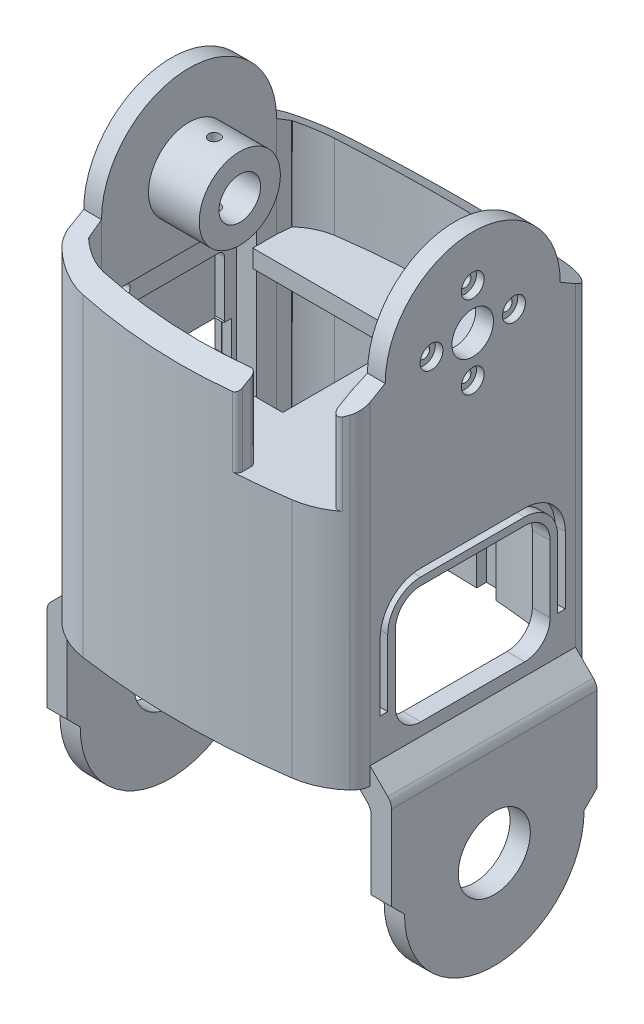
SolidWorks part; units mm, degrees
material "PLA"
ref_plane "Front Plane" through (0, 0, 0) normal (0, 0, 1) x (1, 0, 0)
ref_plane "Top Plane" through (0, 0, 0) normal (0, 1, 0) x (1, 0, 0)
ref_plane "Right Plane" through (0, 0, 0) normal (1, 0, 0) x (0, 0, -1)
sketch "Sketch1" plane through (0, 0, 0) normal (1, 0, 0) x (0, 0, -1)
  line L0 (-17.25, 0) -> (-17.25, -67.25)
  line L1 (17.25, 0) -> (17.25, -67.25)
  line L2 (-17.25, -67.25) -> (17.25, -67.25)
  arc A0 (17.25, 0) -> (-17.25, 0) centre (0, 0) ccw
  circle A1 centre (0, 0) radius 4.1
  circle A2 centre (0, 0) radius 8.125 construction
  circle A3 centre (0, 8.125) radius 1.15
  circle A4 centre (8.125, 0) radius 1.15
  circle A5 centre (-8.125, 0) radius 1.15
  circle A6 centre (0, -8.125) radius 1.15
  dimension "D1" = 34.5
  dimension "D4" = 8.2
  dimension "D5" = 16.25
  dimension "D6" = 2.3
  dimension "D2" = 67.25
  dimension "D3" = 67.25
extrude "Boss-Extrude1" add sketch "Sketch1" along normal blind 3.5
ref_plane "Plane1" through (0, 0, 0) normal (0, -1, 0) x (-1, 0, 0)
ref_plane "Plane2" through (29.7, 0, 0) normal (-1, 0, 0) x (0, 0, 1)
sketch "Sketch2" plane through (0, 0, 0) normal (0, -1, 0) x (-1, 0, 0)
  line L0 (0, -17.25) -> (-59.4, -17.25) construction
  line L1 (-29.7, 0) -> (-29.7, -28) construction
  line L3 (-59.4, -17.25) -> (-59.4, -20.25)
  line L4 (0, -17.25) -> (0, -20.25)
  line L6 (-29.7, -28) -> (-17.6897, -27.7644) construction
  line L7 (-17.6897, -27.7644) -> (-9.1109, -26.529) construction
  line L8 (-9.1109, -26.529) -> (-3.2086, -24.1613) construction
  line L9 (-3.2086, -24.1613) -> (-1.3201, -22.8861) construction
  line L10 (-1.3201, -22.8861) -> (-0.3051, -21.5079) construction
  line L11 (-0.3051, -21.5079) -> (-0.1375, -21.1541) construction
  line L12 (-0.1375, -21.1541) -> (0, -20.25) construction
  line L13 (-3.5, -17.25) -> (-3.7359, -19.9547)
  line L14 (-55.9, -17.25) -> (-55.6641, -19.9547)
  line L15 (-55.9, -17.25) -> (-59.4, -17.25)
  line L17 (0, -17.25) -> (-3.5, -17.25)
  arc A0 (0, -20.25) -> (-1.3201, -22.8861) centre (-4.0147, -19.8881) cw
  arc A1 (-1.3201, -22.8861) -> (-9.1109, -26.529) centre (-11.2153, -11.8765) cw
  arc A2 (-29.7, -28) -> (-9.1109, -26.529) centre (-29.7, 116.8281) ccw
  arc A3 (-29.7, -24.2523) -> (-9.3648, -22.779) centre (-29.7, 116.8281) ccw
  arc A4 (-3.8286, -20.1061) -> (-9.3648, -22.779) centre (-11.2153, -11.8765) cw
  arc A5 (-3.7359, -19.9547) -> (-3.8286, -20.1061) centre (-4.0147, -19.8881) cw
  arc A6 (-29.7, -28) -> (-50.2891, -26.529) centre (-29.7, 116.8281) cw
  arc A7 (-58.0799, -22.8861) -> (-50.2891, -26.529) centre (-48.1847, -11.8765) ccw
  arc A8 (-59.4, -20.25) -> (-58.0799, -22.8861) centre (-55.3853, -19.8881) ccw
  arc A9 (-55.6641, -19.9547) -> (-55.5714, -20.1061) centre (-55.3853, -19.8881) ccw
  arc A10 (-55.5714, -20.1061) -> (-50.0352, -22.779) centre (-48.1847, -11.8765) ccw
  arc A11 (-29.7, -24.2523) -> (-50.0352, -22.779) centre (-29.7, 116.8281) cw
  dimension "D1" = 59.4
extrude "Boss-Extrude2" add sketch "Sketch2" along normal blind 67.25
mirror "Mirror2" about plane through (29.7, 0, 0) normal (-1, 0, 0) of "Boss-Extrude1"
sketch "Sketch3" plane through (0, 0, 0) normal (-1, 0, 0) x (0, 0, 1)
  line L0 (17.25, 0) -> (32.7486, -8.9481)
  line L1 (-1.925, 0) -> (1.925, 0) construction
  line L2 (32.7486, -8.9481) -> (32.7486, 0)
  line L3 (32.7486, 0) -> (17.25, 0)
  arc A0 (17.25, 0) -> (-17.25, 0) centre (0, 0) ccw construction
  dimension "D1" = 30
extrude "Cut-Extrude1" cut sketch "Sketch3" against normal through all
ref_plane "Plane3" through (0, 0, 0) normal (0, 0, -1) x (-1, 0, 0)
mirror "Mirror3" about plane through (0, 0, 0) normal (0, 0, -1) of "Cut-Extrude1", "Boss-Extrude2"
sketch "Sketch4" plane through (0, 0, 0) normal (-1, 0, 0) x (0, 0, 1)
  line L0 (-20.25, -67.25) -> (-20.25, -1.7321) construction
  line L1 (-13.25, -13.5) -> (13.25, -13.5)
  line L2 (-13.25, -13.5) -> (-13.25, -60.75)
  line L3 (-13.25, -60.75) -> (13.25, -60.75)
  line L4 (13.25, -13.5) -> (13.25, -60.75)
  line L5 (20.25, -67.25) -> (20.25, -1.7321) construction
  line L6 (20.25, -67.25) -> (-20.25, -67.25) construction
  dimension "D1" = 7
  dimension "D2" = 7
  dimension "D3" = 13.5
  dimension "D4" = 6.5
extrude "Cut-Extrude2" cut sketch "Sketch4" against normal blind 3.5
sketch "Sketch6" plane through (0, 0, 0) normal (-1, 0, 0) x (0, 0, 1)
  line L8 (-15.75, -63.25) -> (15.75, -63.25)
  line L9 (-15.75, -11) -> (-15.75, -63.25)
  line L10 (15.75, -63.25) -> (15.75, -11)
  line L11 (15.75, -11) -> (-15.75, -11)
  line L12 (-15.75, -63.25) -> (15.75, -63.25)
  line L13 (-15.75, -11) -> (-15.75, -63.25)
  line L14 (15.75, -63.25) -> (15.75, -11)
  line L15 (15.75, -11) -> (-15.75, -11)
  dimension "D1" = 2.5
extrude "Boss-Extrude3" add sketch "Sketch6" along normal blind 2
chamfer "Chamfer2" distance 2 angle 45 4 edges at (-2, -63.25, 0) (-2, -37.125, 15.75) (-2, -37.125, -15.75) (-2, -11, 0)
sketch "Sketch7" plane through (0, 0, 0) normal (1, 0, 0) x (0, 0, -1)
  line L4 (-13.25, -60.75) -> (13.25, -60.75)
  line L5 (13.25, -60.75) -> (13.25, -13.5)
  line L6 (13.25, -13.5) -> (-13.25, -13.5)
  line L7 (-13.25, -13.5) -> (-13.25, -60.75)
  line L8 (-13.25, -60.75) -> (13.25, -60.75)
  line L9 (13.25, -60.75) -> (13.25, -13.5)
  line L10 (13.25, -13.5) -> (-13.25, -13.5)
  line L11 (-13.25, -13.5) -> (-13.25, -60.75)
  dimension "D1" = 0
extrude "Cut-Extrude3" cut sketch "Sketch7" against normal blind 0.8
sketch "Sketch8" plane through (-2, 0, 0) normal (-1, 0, 0) x (0, 0, 1)
  line L0 (15.75, -63.25) -> (15.75, -11) construction
  line L1 (-10.6511, -32.25) -> (10.75, -32.25)
  line L2 (-10.6511, -32.25) -> (-10.6511, -38.75)
  line L3 (-10.6511, -38.75) -> (10.75, -38.75)
  line L4 (10.75, -32.25) -> (10.75, -38.75)
  line L5 (-15.75, -11) -> (-15.75, -63.25) construction
  line L6 (15.75, -11) -> (-15.75, -11) construction
  line L7 (-15.75, -63.25) -> (15.75, -63.25) construction
  dimension "D1" = 5
  dimension "D2" = 5.0989
  dimension "D3" = 21.25
  dimension "D4" = 24.5
extrude "Cut-Extrude4" cut sketch "Sketch8" against normal up to next
sketch "Sketch9" plane through (59.4, 0, 0) normal (1, 0, 0) x (0, 0, -1)
  circle A0 centre (0, -49.64) radius 7.1
  dimension "D1" = 14.2
extrude "Cut-Extrude5" cut sketch "Sketch9" against normal up to next
ref_plane "Plane4" through (0, -19.75, 0) normal (0, -1, 0) x (-1, 0, 0)
sketch "Sketch10" plane through (0, -19.75, 0) normal (0, -1, 0) x (-1, 0, 0)
  line L0 (-55.6641, -19.9547) -> (-55.9, -17.25) construction
  line L1 (-3.5, -17.25) -> (-3.7359, -19.9547) construction
  line L3 (-3.5, -17.25) -> (-3.5, 17.25) construction
  line L6 (-3.5, 17.25) -> (-3.7359, 19.9547) construction
  line L7 (-55.9, -17.25) -> (-55.9, 17.25) construction
  line L8 (-55.6641, 19.9547) -> (-55.9, 17.25) construction
  line L9 (-55.6641, -19.9547) -> (-55.9, -17.25)
  line L10 (-3.5, -17.25) -> (-3.7359, -19.9547)
  line L11 (-3.5, -17.25) -> (-3.5, -12.56)
  line L12 (-3.5, 17.25) -> (-3.7359, 19.9547)
  line L13 (-55.9, -17.25) -> (-55.9, 17.25)
  line L14 (-55.6641, 19.9547) -> (-55.9, 17.25)
  line L15 (-18.2613, -12.36) -> (-18.2613, -12.56) construction
  line L16 (-12.72, -12.36) -> (-25.62, -12.36) construction
  line L17 (-3.5, -12.56) -> (-34.52, -12.56)
  line L18 (-34.52, -12.56) -> (-34.52, 12.56)
  line L19 (-3.5, 12.56) -> (-3.5, 17.25)
  line L43 (-34.52, 12.56) -> (-3.5, 12.56)
  line L45 (-25.62, 12.36) -> (-12.72, 12.36) construction
  line L46 (-34.52, 5) -> (-34.52, 13.1992) construction
  line L47 (-31.62, 5) -> (-35.82, 5) construction
  line L48 (-34.32, 6.7) -> (-34.32, 5.6557) construction
  arc A0 (-55.6641, -19.9547) -> (-55.5714, -20.1061) centre (-55.3853, -19.8881) ccw construction
  arc A1 (-50.0352, -22.779) -> (-9.3648, -22.779) centre (-29.7, 116.8281) ccw construction
  arc A2 (-55.5714, -20.1061) -> (-50.0352, -22.779) centre (-48.1847, -11.8765) ccw construction
  arc A3 (-9.3648, -22.779) -> (-3.8286, -20.1061) centre (-11.2153, -11.8765) ccw construction
  arc A4 (-3.8286, -20.1061) -> (-3.7359, -19.9547) centre (-4.0147, -19.8881) ccw construction
  arc A5 (-3.7359, 19.9547) -> (-3.8286, 20.1061) centre (-4.0147, 19.8881) ccw construction
  arc A6 (-3.8286, 20.1061) -> (-9.3648, 22.779) centre (-11.2153, 11.8765) ccw construction
  arc A7 (-9.3648, 22.779) -> (-50.0352, 22.779) centre (-29.7, -116.8281) ccw construction
  arc A8 (-55.5714, 20.1061) -> (-55.6641, 19.9547) centre (-55.3853, 19.8881) ccw construction
  arc A9 (-50.0352, 22.779) -> (-55.5714, 20.1061) centre (-48.1847, 11.8765) ccw construction
  arc A30 (-55.6641, -19.9547) -> (-55.5714, -20.1061) centre (-55.3853, -19.8881) ccw
  arc A31 (-50.0352, -22.779) -> (-9.3648, -22.779) centre (-29.7, 116.8281) ccw
  arc A32 (-55.5714, -20.1061) -> (-50.0352, -22.779) centre (-48.1847, -11.8765) ccw
  arc A33 (-9.3648, -22.779) -> (-3.8286, -20.1061) centre (-11.2153, -11.8765) ccw
  arc A34 (-3.8286, -20.1061) -> (-3.7359, -19.9547) centre (-4.0147, -19.8881) ccw
  arc A35 (-3.7359, 19.9547) -> (-3.8286, 20.1061) centre (-4.0147, 19.8881) ccw
  arc A36 (-3.8286, 20.1061) -> (-9.3648, 22.779) centre (-11.2153, 11.8765) ccw
  arc A37 (-9.3648, 22.779) -> (-50.0352, 22.779) centre (-29.7, -116.8281) ccw
  arc A38 (-55.5714, 20.1061) -> (-55.6641, 19.9547) centre (-55.3853, 19.8881) ccw
  arc A39 (-50.0352, 22.779) -> (-55.5714, 20.1061) centre (-48.1847, 11.8765) ccw
  dimension "D1" = 0.2
  dimension "D2" = 0.2
  dimension "D3" = 0.2
extrude "Boss-Extrude4" add sketch "Sketch10" along normal blind 3.5
sketch "Sketch11" plane through (0, -23.25, 0) normal (0, -1, 0) x (-1, 0, 0)
  line L0 (-36.07, -6.9) -> (-40.07, -6.9) construction
  line L2 (-36.07, -6.9) -> (-36.07, -24.1084) construction
  line L3 (-40.07, -6.9) -> (-40.07, -24.1084) construction
  line L5 (-36.07, -24.1084) -> (-40.07, -24.1084)
  line L6 (-36.07, -24.1084) -> (-36.07, 25.609)
  line L7 (-36.07, 25.609) -> (-40.07, 25.609)
  line L8 (-40.07, -24.1084) -> (-40.07, 25.609)
  arc A0 (-50.0352, -22.779) -> (-9.3648, -22.779) centre (-29.7, 116.8281) ccw construction
  dimension "D1" = 4
extrude "Boss-Extrude5" add sketch "Sketch11" along normal blind 40
sketch "Sketch12" plane through (40.07, 0, 0) normal (1, 0, 0) x (0, 0, -1)
  circle A0 centre (0, -49.64) radius 7.1
extrude "Cut-Extrude6" cut sketch "Sketch12" against normal blind 10
chamfer "Chamfer3" distance 1 angle 45 1 edges at (36.07, -23.25, 0)
chamfer "Chamfer4" distance 1 angle 45 1 edges at (40.07, -23.25, 0)
fillet "Fillet1" radius 3 2 edges at (38.0708, -63.25, -24.0037) (38.0708, -63.25, 24.0037)
sketch "Sketch13" plane through (59.4, 0, 0) normal (1, 0, 0) x (0, 0, -1)
  circle A0 centre (0, -49.64) radius 9
  circle A1 centre (0, -49.64) radius 5.5
  dimension "D1" = 18
  dimension "D2" = 11
extrude "Boss-Extrude6" add sketch "Sketch13" along normal blind 1.5
sketch "Sketch16" plane through (60.9, 0, 0) normal (1, 0, 0) x (0, 0, -1)
  circle A0 centre (0, -49.64) radius 9
extrude "Boss-Extrude7" add sketch "Sketch16" along normal blind 1
fillet "Fillet2" radius 1 1 edges at (61.9, -49.64, -9)
ref_plane "Plane5" through (0, 0, 20.25) normal (0, 0, -1) x (-1, 0, 0)
sketch "Sketch17" plane through (0, 0, 20.25) normal (0, 0, -1) x (-1, 0, 0)
  line L0 (-59.4, -67.25) -> (-55.9, -67.25) construction
  line L1 (-59.4, -67.25) -> (-59.4, -70.75) construction
  line L3 (-55.9, -67.25) -> (-59.4, -70.75) construction
  line L4 (-59.4, -67.25) -> (-59.65, -67.25) construction
  line L5 (-59.4, -70.75) -> (-59.65, -71) construction
  line L6 (-59.65, -71) -> (-59.65, -105.91) construction
  line L7 (-59.4, -67.25) -> (-59.4, -63.75) construction
  line L8 (-59.4, -63.75) -> (-64.5645, -68.9145) construction
  line L9 (-59.65, -105.91) -> (-63.15, -105.91)
  line L10 (-63.15, -105.91) -> (-63.15, -67.5)
  line L11 (-63.15, -67.5) -> (-59.4, -63.75)
  line L12 (-59.4, -63.75) -> (-59.4, -67.25)
  line L13 (-59.4, -67.25) -> (-55.9, -67.25)
  line L14 (-55.9, -67.25) -> (-59.65, -71)
  line L15 (-59.65, -71) -> (-59.65, -105.91)
  dimension "D2" = 3.5
  dimension "D3" = 0.25
  dimension "D4" = 3.5
  dimension "D5" = 45
  dimension "D6" = 3.5
  dimension "D7" = 34.91
sketch "Sketch18" plane through (55.9, 0, 0) normal (-1, 0, 0) x (0, 0, 1)
  circle A0 centre (0, -49.64) radius 9
  circle A1 centre (0, -49.64) radius 7.1
  circle A2 centre (0, -49.64) radius 7.1
  dimension "D2" = 18
  dimension "D1" = 0
extrude "Boss-Extrude8" add sketch "Sketch18" along normal blind 0.5
chamfer "Chamfer5" distance 0.5 angle 45 1 edges at (55.9, -49.64, 9)
extrude "Boss-Extrude9" add sketch "Sketch17" along normal blind 40.5
sketch "Sketch19" plane through (63.15, 0, 0) normal (1, 0, 0) x (0, 0, -1)
  line L0 (-17.7, -88.21) -> (-20.25, -85.66)
  line L1 (-20.25, -85.66) -> (-20.25, -105.91)
  line L2 (20.25, -105.91) -> (-20.25, -105.91) construction
  line L3 (0, -105.91) -> (0, -88.21) construction
  line L4 (-20.25, -67.5) -> (-20.25, -105.91) construction
  line L5 (17.7, -88.21) -> (20.25, -85.66)
  line L6 (-20.25, -105.91) -> (0, -105.91)
  line L7 (20.25, -67.5) -> (20.25, -105.91) construction
  line L8 (0, -105.91) -> (20.25, -105.91)
  line L9 (20.25, -105.91) -> (20.25, -85.66)
  arc A0 (-17.7, -88.21) -> (17.7, -88.21) centre (0, -88.21) ccw
  line M5 (-20.25, -67.5) -> (-20.25, -105.91)
  line M6 (-20.25, -105.91) -> (20.25, -105.91)
  line M7 (20.25, -105.91) -> (20.25, -67.5)
  dimension "D1" = 17.7
  dimension "D2" = 45
  dimension "D3" = 45
extrude "Cut-Extrude8" cut sketch "Sketch19" against normal up to next contours A0 L0 M5 M6 | A0 L5 M6 M7
chamfer "Chamfer6" distance 1.5 angle 45 1 edges at (59.4, -49.64, 9)
sketch "Sketch20" plane through (63.15, 0, 0) normal (1, 0, 0) x (0, 0, -1)
  line L0 (0, -49.64) -> (0, -86.64) construction
  circle A0 centre (0, -86.64) radius 7.1
  dimension "D2" = 14.2
  dimension "D1" = 37
extrude "Cut-Extrude9" cut sketch "Sketch20" against normal up to next
sketch "Sketch21" plane through (0, 0, 0) normal (-1, 0, 0) x (0, 0, 1)
  circle A0 centre (0, 8.125) radius 1.5
  circle A1 centre (8.125, 0) radius 1.5
  circle A2 centre (0, -8.125) radius 1.5
  circle A3 centre (-8.125, 0) radius 1.5
  dimension "D1" = 3
extrude "Boss-Extrude10" add sketch "Sketch21" against normal blind 3.5
mirror "Mirror4" about plane through (29.7, 0, 0) normal (-1, 0, 0) of "Cut-Extrude9", "Cut-Extrude8", "Boss-Extrude9"
sketch "Sketch22" plane through (-2, 0, 0) normal (-1, 0, 0) x (0, 0, 1)
  circle A0 centre (0, -49.64) radius 3.75
  dimension "D1" = 7.5
extrude "Cut-Extrude10" cut sketch "Sketch22" against normal up to next
sketch "Sketch23" plane through (-0.8, 0, 0) normal (1, 0, 0) x (0, 0, -1)
  line L65 (10.8, -38.89) -> (7, -38.89)
  line L66 (10.8, -32.115) -> (10.8, -38.89)
  line L67 (9.303, -32.115) -> (10.8, -32.115)
  line L68 (9.4423, -31.8921) -> (9.303, -32.115)
  line L69 (9.4423, -20.9369) -> (9.4423, -31.8921)
  line L70 (-8.2423, -19.7369) -> (8.2423, -19.7369)
  line L71 (-9.4423, -31.8921) -> (-9.4423, -20.9369)
  line L72 (-9.303, -32.115) -> (-9.4423, -31.8921)
  line L73 (-10.8, -32.115) -> (-9.303, -32.115)
  line L74 (-10.8, -38.89) -> (-10.8, -32.115)
  line L75 (-7, -38.89) -> (-10.8, -38.89)
  line L76 (-7, -40.6536) -> (-7, -38.89)
  line L77 (-11.36, -43.6785) -> (-9.7065, -43.6785)
  line L78 (-11.86, -16.5298) -> (-11.86, -43.1785)
  line L79 (10.3601, -15.03) -> (-10.3604, -15.03)
  line L80 (11.86, -43.1784) -> (11.86, -16.5295)
  line L81 (9.7065, -43.6785) -> (11.36, -43.6785)
  line L82 (7, -38.89) -> (7, -40.6536)
  line L83 (10.8, -38.89) -> (7, -38.89)
  line L84 (10.8, -32.115) -> (10.8, -38.89)
  line L85 (9.303, -32.115) -> (10.8, -32.115)
  line L86 (9.4423, -31.8921) -> (9.303, -32.115)
  line L87 (9.4423, -20.9369) -> (9.4423, -31.8921)
  line L88 (-8.2423, -19.7369) -> (8.2423, -19.7369)
  line L89 (-9.4423, -31.8921) -> (-9.4423, -20.9369)
  line L90 (-9.303, -32.115) -> (-9.4423, -31.8921)
  line L91 (-10.8, -32.115) -> (-9.303, -32.115)
  line L92 (-10.8, -38.89) -> (-10.8, -32.115)
  line L93 (-7, -38.89) -> (-10.8, -38.89)
  line L94 (-7, -40.6536) -> (-7, -38.89)
  line L95 (-11.36, -43.6785) -> (-9.7065, -43.6785)
  line L96 (-11.86, -16.5298) -> (-11.86, -43.1785)
  line L97 (10.3601, -15.03) -> (-10.3604, -15.03)
  line L98 (11.86, -43.1784) -> (11.86, -16.5295)
  line L99 (9.7065, -43.6785) -> (11.36, -43.6785)
  line L100 (7, -38.89) -> (7, -40.6536)
  circle A28 centre (-10.25, -16.89) radius 1.15
  circle A29 centre (10.25, -16.89) radius 1.15
  circle A30 centre (10.25, -41.34) radius 1.15
  circle A31 centre (-10.25, -41.34) radius 1.15
  arc A40 (9.4423, -20.9369) -> (8.2423, -19.7369) centre (8.2423, -20.9369) ccw
  arc A41 (-8.2423, -19.7369) -> (-9.4423, -20.9369) centre (-8.2423, -20.9369) ccw
  arc A42 (-7, -40.6536) -> (-9.7065, -43.6785) centre (0, -49.64) ccw
  arc A43 (-11.86, -43.1785) -> (-11.36, -43.6785) centre (-11.36, -43.1785) ccw
  arc A44 (11.36, -43.6785) -> (11.86, -43.1784) centre (11.36, -43.1785) ccw
  arc A45 (9.7065, -43.6785) -> (7, -40.6536) centre (0, -49.64) ccw
  arc A46 (9.4423, -20.9369) -> (8.2423, -19.7369) centre (8.2423, -20.9369) ccw
  arc A47 (-8.2423, -19.7369) -> (-9.4423, -20.9369) centre (-8.2423, -20.9369) ccw
  arc A48 (-7, -40.6536) -> (-9.7065, -43.6785) centre (0, -49.64) ccw
  arc A49 (-11.86, -43.1785) -> (-11.36, -43.6785) centre (-11.36, -43.1785) ccw
  arc A50 (11.36, -43.6785) -> (11.86, -43.1784) centre (11.36, -43.1785) ccw
  arc A51 (9.7065, -43.6785) -> (7, -40.6536) centre (0, -49.64) ccw
  spline S4 degree 3 poles (532.7218, -2965.2554) (46.0734, -186.7644) (2.6461, -12.4021) (-10.7484, -15.0781) (-10.8437, -15.1068) (-11.0252, -15.182) (-11.1112, -15.2282) (-11.2742, -15.337) (-11.3514, -15.4001) (-11.5587, -15.6075) (-11.6705, -15.7746) (-16.0328, -26.295) (93.5141, -90.5306) (1392.4975, 2631.509) knots -17.228517 -17.228517 -17.228517 -17.228517 0.125 0.125 0.25 0.25 0.375 0.375 0.5 0.5 0.75 0.75 15.088906 15.088906 15.088906 15.088906 only from (-10.3604, -15.03) to (-11.86, -16.5298)
  spline S5 degree 3 poles (-2938.3132, -559.6797) (-159.8816, -72.9698) (14.4883, -29.5363) (11.8119, -16.1415) (11.7831, -16.0463) (11.708, -15.8648) (11.6618, -15.7788) (11.553, -15.6158) (11.4898, -15.5386) (11.2825, -15.3312) (11.1153, -15.2194) (0.5947, -10.8574) (-63.6396, -120.4095) (2658.5366, -1419.1506) knots -17.228977 -17.228977 -17.228977 -17.228977 0.125 0.125 0.25 0.25 0.375 0.375 0.5 0.5 0.75 0.75 15.089089 15.089089 15.089089 15.089089 only from (11.86, -16.5295) to (10.3601, -15.03)
  spline S6 degree 3 poles (-10.3604, -15.03) (-10.4595, -15.0298) (-10.5568, -15.0398) (-10.7484, -15.0781) (-10.8437, -15.1068) (-11.0252, -15.182) (-11.1112, -15.2282) (-11.2742, -15.337) (-11.3514, -15.4001) (-11.5587, -15.6075) (-11.6705, -15.7746) (-11.82, -16.1352) (-11.8602, -16.3318) (-11.86, -16.5298) knots 0 0 0 0 0.125 0.125 0.25 0.25 0.375 0.375 0.5 0.5 0.75 0.75 1 1 1 1
  spline S7 degree 3 poles (11.86, -16.5295) (11.8602, -16.4305) (11.8502, -16.3331) (11.8119, -16.1415) (11.7831, -16.0463) (11.708, -15.8648) (11.6618, -15.7788) (11.553, -15.6158) (11.4898, -15.5386) (11.2825, -15.3312) (11.1153, -15.2194) (10.7548, -15.0699) (10.5581, -15.0298) (10.3601, -15.03) knots 0 0 0 0 0.125 0.125 0.25 0.25 0.375 0.375 0.5 0.5 0.75 0.75 1 1 1 1
  dimension "D2" = 2.3
  dimension "D3" = 2.3
  dimension "D4" = 2.3
  dimension "D5" = 2.3
  dimension "D1" = 0.2
extrude "Boss-Extrude11" add sketch "Sketch23" along normal offset from surface (1.82 mm away) 0.2
sketch "Sketch24" plane through (36.07, 0, 0) normal (-1, 0, 0) x (0, 0, 1)
  line L1 (-13, -29.275) -> (-8, -29.275)
  line L2 (-13, -29.275) -> (-13, -45.2091)
  line L3 (-13, -45.2091) -> (-8, -45.2091)
  line L4 (-8, -29.275) -> (-8, -45.2091)
  line L5 (8, -29.275) -> (13, -29.275)
  line L6 (8, -29.275) -> (8, -45.2091)
  line L7 (8, -45.2091) -> (13, -45.2091)
  line L8 (13, -29.275) -> (13, -45.2091)
  circle A0 centre (-10.25, -41.34) radius 1.15
  circle A9 centre (10.25, -41.34) radius 1.15
  dimension "D5" = 2.3
  dimension "D6" = 2.3
  dimension "D1" = 5
  dimension "D2" = 13
  dimension "D3" = 13
  dimension "D4" = 5
extrude "Boss-Extrude12" add sketch "Sketch24" along a picked direction on the side of the normal up to next (2.65 mm away)
sketch "Sketch25" plane through (36.07, 0, 0) normal (-1, 0, 0) x (0, 0, 1)
  circle A4 centre (10.25, -41.34) radius 1.15 construction
  circle A5 centre (-10.25, -41.34) radius 1.15 construction
  circle A6 centre (10.25, -41.34) radius 1.15
  circle A7 centre (-10.25, -41.34) radius 1.15
extrude "Cut-Extrude11" cut sketch "Sketch25" against normal up to next
sketch "Sketch26" plane through (0, 0, 0) normal (-1, 0, 0) x (0, 0, 1)
  circle A1 centre (0, 0) radius 13.375
  dimension "D1" = 26.75
extrude "Cut-Extrude12" cut sketch "Sketch26" along normal blind 3.3
sketch "Sketch27" plane through (-2, 0, 0) normal (-1, 0, 0) x (0, 0, 1)
  circle A0 centre (0, -49.64) radius 5
  dimension "D1" = 10
extrude "Boss-Extrude13" add sketch "Sketch27" along normal blind 1
fillet "Fillet7" radius 0.75 1 edges at (-3, -49.64, 5)
sketch "Sketch28" plane through (3.5, 0, 0) normal (1, 0, 0) x (0, 0, -1)
  circle A0 centre (0, 0) radius 4.1
  circle A1 centre (0, 0) radius 8
  dimension "D1" = 8.2
  dimension "D2" = 16
extrude "Boss-Extrude14" add sketch "Sketch28" along normal blind 1.5
sketch "Sketch29" plane through (5, 0, 0) normal (1, 0, 0) x (0, 0, -1)
  circle A0 centre (0, 0) radius 4.1
  circle A1 centre (0, 0) radius 8
  dimension "D1" = 8.2
  dimension "D2" = 16
extrude "Boss-Extrude15" add sketch "Sketch29" along normal blind 8.5
sketch "Sketch30" plane through (0, 0, 0) normal (0, -1, 0) x (-1, 0, 0)
  line L0 (-13.5, 0) -> (-3.5, 0) construction
  line L1 (-13.5, 8) -> (-13.5, -8) construction
  circle A0 centre (-8.5, 0) radius 1.125
  dimension "D2" = 2.25
  dimension "D1" = 10
extrude "Cut-Extrude13" cut sketch "Sketch30" against normal through all and the other way blind 15
sketch "Sketch31" plane through (-3.75, 0, 0) normal (-1, 0, 0) x (0, 0, 1)
  line L5 (-20.25, -85.66) -> (-17.7, -88.21)
  line L7 (20.25, -85.66) -> (20.25, -67.5)
  line L8 (20.25, -67.5) -> (-20.25, -67.5)
  line L9 (-20.25, -67.5) -> (-20.25, -85.66)
  line L12 (20.25, -85.66) -> (20.25, -67.5)
  line L13 (20.25, -67.5) -> (-20.25, -67.5)
  line L14 (-20.25, -67.5) -> (-20.25, -85.66)
  line L15 (-20.25, -85.66) -> (-17.7, -88.21)
  line L17 (17.7, -88.21) -> (20.25, -85.66)
  line L18 (17.7, -88.21) -> (20.25, -85.66)
  circle A0 centre (0, -86.64) radius 7.1 construction
  arc A1 (-17.7, -88.21) -> (17.7, -88.21) centre (0, -88.21) ccw
  circle A3 centre (0, -86.64) radius 7.1
  arc A6 (-17.7, -88.21) -> (17.7, -88.21) centre (0, -88.21) ccw
  circle M7 centre (0, -86.64) radius 7.1
  line M8 (-20.25, -85.66) -> (-17.7, -88.21)
  arc M9 (-17.7, -88.21) -> (17.7, -88.21) centre (0, -88.21) ccw
  line M10 (17.7, -88.21) -> (20.25, -85.66)
  line M11 (20.25, -85.66) -> (20.25, -67.5)
  line M12 (20.25, -67.5) -> (-20.25, -67.5)
  line M13 (-20.25, -67.5) -> (-20.25, -85.66)
  dimension "D1" = 0
extrude "Boss-Extrude16" add sketch "Sketch31" along normal blind 0.5 contours M13 M8 M9 M10 M11 M12 M7
chamfer "Chamfer7" distance 0.5 angle 45 3 edges at (-4, -67.5, -20.25) (-4, -67.5, 20.25) (-4.25, -67.5, 0)
ref_plane "Plane6" through (29.7, 0, 0) normal (1, 0, 0) x (0, 0, -1)
mirror "Mirror5" about plane through (29.7, 0, 0) normal (1, 0, 0) of "Chamfer7", "Boss-Extrude16"
fillet "Fillet8" radius 2.5 4 edges at (59.65, -71, 0) (-0.25, -71, 0) (-4.25, -68, 0) (63.65, -68, 0)
sketch "Sketch32" plane through (59.4, 0, 0) normal (1, 0, 0) x (0, 0, -1)
  line L0 (20.25, -63.75) -> (-20.25, -63.75) construction
  line L1 (-15.25, -38.03) -> (15.25, -38.03)
  line L2 (-15.25, -38.03) -> (-15.25, -61.25)
  line L3 (-15.25, -61.25) -> (15.25, -61.25)
  line L4 (15.25, -38.03) -> (15.25, -61.25)
  line L5 (20.25, -63.75) -> (20.25, -1.7321) construction
  line L6 (-20.25, -32.67) -> (-20.25, 32.67) construction
  dimension "D1" = 2.5
  dimension "D2" = 5
  dimension "D3" = 5
  dimension "D4" = 23.22
extrude "Cut-Extrude14" cut sketch "Sketch32" against normal blind 10 and the other way blind 10
fillet "Fillet9" radius 5 4 edges at (57.65, -61.25, -15.25) (57.65, -61.25, 15.25) (57.65, -38.03, 15.25) (57.65, -38.03, -15.25)
sketch "Sketch33" plane through (59.4, 0, 0) normal (1, 0, 0) x (0, 0, -1)
  line L5 (-18.25, -56.25) -> (-16.75, -56.25)
  line L6 (16.75, -56.25) -> (18.25, -56.25)
  line L8 (16.75, -56.25) -> (16.75, -43.03)
  line L9 (10.25, -36.53) -> (-10.25, -36.53)
  line L10 (-16.75, -43.03) -> (-16.75, -56.25)
  line L11 (16.75, -56.25) -> (16.75, -43.03)
  line L12 (10.25, -36.53) -> (-10.25, -36.53)
  line L13 (-16.75, -43.03) -> (-16.75, -56.25)
  line L36 (18.25, -56.25) -> (18.25, -43.03)
  line L37 (10.25, -35.03) -> (-10.25, -35.03)
  line L38 (-18.25, -43.03) -> (-18.25, -56.25)
  line L39 (18.25, -56.25) -> (18.25, -43.03)
  line L40 (10.25, -35.03) -> (-10.25, -35.03)
  line L41 (-18.25, -43.03) -> (-18.25, -56.25)
  arc A6 (16.75, -43.03) -> (10.25, -36.53) centre (10.25, -43.03) ccw
  arc A7 (-10.25, -36.53) -> (-16.75, -43.03) centre (-10.25, -43.03) ccw
  arc A8 (16.75, -43.03) -> (10.25, -36.53) centre (10.25, -43.03) ccw
  arc A9 (-10.25, -36.53) -> (-16.75, -43.03) centre (-10.25, -43.03) ccw
  arc A28 (18.25, -43.03) -> (10.25, -35.03) centre (10.25, -43.03) ccw
  arc A29 (-10.25, -35.03) -> (-18.25, -43.03) centre (-10.25, -43.03) ccw
  arc A30 (18.25, -43.03) -> (10.25, -35.03) centre (10.25, -43.03) ccw
  arc A31 (-10.25, -35.03) -> (-18.25, -43.03) centre (-10.25, -43.03) ccw
  dimension "D1" = 3
  dimension "D2" = 1.5
extrude "Cut-Extrude15" cut sketch "Sketch33" against normal blind 2
sketch "Sketch34" plane through (59.4, 0, 0) normal (1, 0, 0) x (0, 0, -1)
  circle A10 centre (0, 8.125) radius 2.25
  circle A11 centre (8.125, 0) radius 2.25
  circle A12 centre (0, -8.125) radius 2.25
  circle A13 centre (-8.125, 0) radius 2.25
  dimension "D1" = 4.5
  dimension "D2" = 4.5
  dimension "D3" = 4.5
  dimension "D4" = 4.5
extrude "Cut-Extrude16" cut sketch "Sketch34" against normal blind 1.5
sketch "Sketch35" plane through (0, 0, 20.25) normal (0, 0, 1) x (1, 0, 0)
  line L0 (40.65, 17.25) -> (40.65, -17.25) construction
  line L1 (40.65, 2) -> (55.65, 2)
  line L2 (40.65, 2) -> (40.65, -19.75)
  line L3 (40.65, -19.75) -> (55.65, -19.75)
  line L4 (55.65, 2) -> (55.65, -19.75)
  line L5 (55.65, -17.25) -> (55.65, 17.25) construction
  line L6 (55.9, 0) -> (59.4, 0) construction
  dimension "D1" = 2
  dimension "D2" = 21.75
extrude "Cut-Extrude17" cut sketch "Sketch35" along normal through all and the other way blind 2
fillet "Fillet10" radius 1 2 edges at (40.65, -12.8586, 27.5855) (55.65, -12.0138, 24.6591)
fillet "Fillet11" radius 1 1 edges at (40.65, -11.7735, 23.8267)
sketch "Sketch36" plane through (1.02, 0, 0) normal (1, 0, 0) x (0, 0, -1)
  circle A8 centre (10.25, -41.34) radius 1.15 construction
  circle A9 centre (10.25, -16.89) radius 1.15 construction
  circle A10 centre (-10.25, -16.89) radius 1.15 construction
  circle A11 centre (-10.25, -41.34) radius 1.15 construction
  circle A12 centre (10.25, -41.34) radius 1.15
  circle A13 centre (10.25, -16.89) radius 1.15
  circle A14 centre (-10.25, -16.89) radius 1.15
  circle A15 centre (-10.25, -41.34) radius 1.15
extrude "Cut-Extrude18" cut sketch "Sketch36" against normal through all
sketch "Sketch37" plane through (0, -63.25, 0) normal (0, -1, 0) x (1, 0, 0)
  line L0 (36.07, 24.1084) -> (36.07, -24.1084) construction
  line L2 (31.9354, -24.2346) -> (31.9354, 24.2346)
  line L4 (41.1443, -23.7873) -> (41.1443, 23.7873)
  line L6 (36.07, 24.1084) -> (36.07, 26.0079)
  line L7 (36.07, 26.0079) -> (40.07, 26.0079)
  line L8 (40.07, 23.8706) -> (40.07, 26.0079)
  line L9 (40.07, 20.8623) -> (40.07, 23.8706) construction
  line L10 (38.07, 26.0079) -> (38.07, 27.7579) construction
  line L11 (31.9354, 0) -> (8.5, 0) construction
  line L13 (36.07, -24.1084) -> (36.07, -26.0079)
  line L14 (36.07, -26.0079) -> (40.07, -26.0079)
  line L15 (40.07, -23.8706) -> (40.07, -26.0079)
  line L16 (38.07, -26.0079) -> (38.07, -27.7579) construction
  line L17 (41.1443, 0) -> (63.65, 0) construction
  line L18 (63.65, -17.7) -> (63.65, 17.7) construction
  arc A0 (9.3648, -22.779) -> (50.0352, -22.779) centre (29.7, 116.8281) ccw construction
  arc A1 (50.0352, 22.779) -> (9.3648, 22.779) centre (29.7, -116.8281) ccw construction
  arc A2 (31.9354, -24.2346) -> (36.07, -24.1084) centre (29.7, 116.8281) ccw
  arc A3 (41.1443, 23.7873) -> (40.07, 23.8706) centre (29.7, -116.8281) ccw
  arc A4 (50.2891, 26.529) -> (9.1109, 26.529) centre (29.7, -116.8281) ccw construction
  arc A5 (9.1109, -26.529) -> (50.2891, -26.529) centre (29.7, 116.8281) ccw construction
  arc A6 (36.07, 24.1084) -> (31.9354, 24.2346) centre (29.7, -116.8281) ccw
  arc A7 (40.07, -23.8706) -> (41.1443, -23.7873) centre (29.7, 116.8281) ccw
  line M13 (36.07, 21.1053) -> (36.07, -21.1053)
  arc M14 (36.07, -21.1053) -> (40.07, -20.8623) centre (29.7, 116.8281) ccw
  line M15 (40.07, -20.8623) -> (40.07, 20.8623)
  arc M16 (40.07, 20.8623) -> (36.07, 21.1053) centre (29.7, -116.8281) ccw
  dimension "D1" = 0
  dimension "D2" = 0
  dimension "D3" = 1.75
  dimension "D4" = 1.75
extrude "Cut-Extrude20" cut sketch "Sketch37" against normal up to surface (40 mm away) and the other way blind 10 contours L15 A7 L4 A3 L8 L7 L6 A6 L2 A2 L13 L14 M13 M16 M15 M14 | M16 M13 M14 M15 up to face at (12.0983, -23.25, 0)
